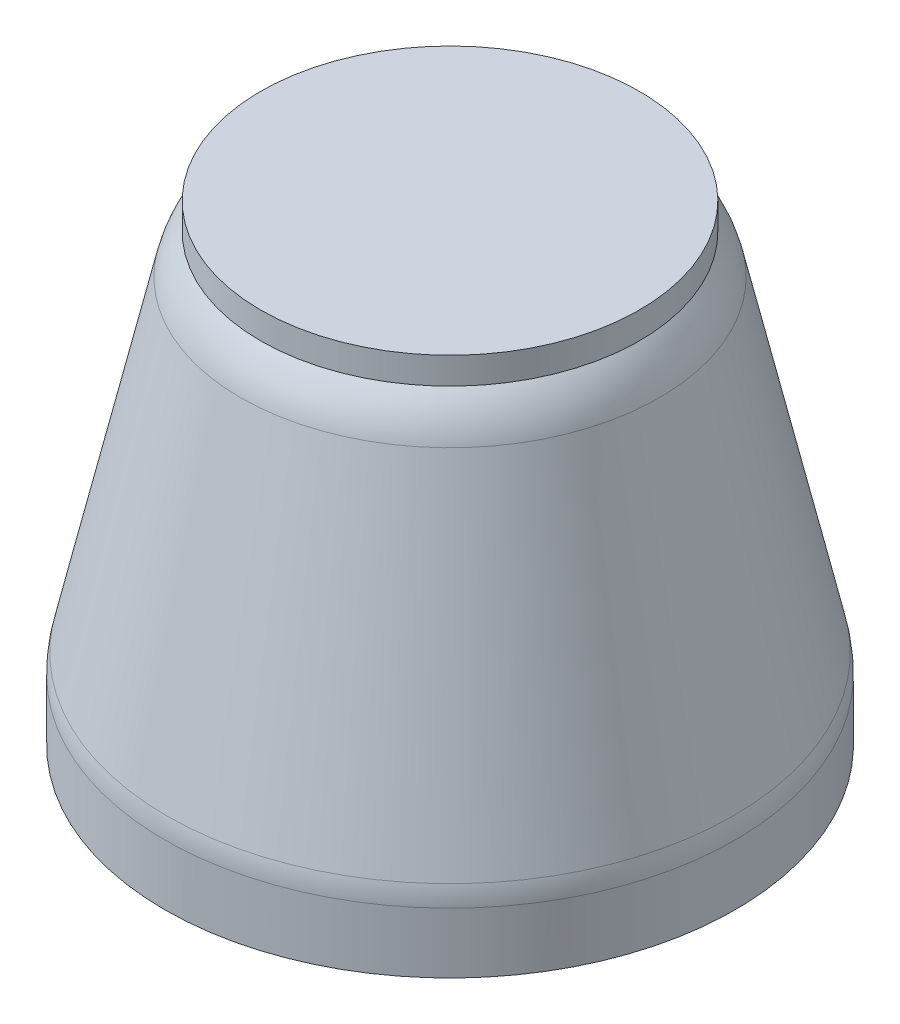
SolidWorks part; units mm, degrees
material "1060 Alloy"
ref_plane "Front Plane" through (0, 0, 0) normal (0, 0, 1) x (1, 0, 0)
ref_plane "Top Plane" through (0, 0, 0) normal (0, 1, 0) x (1, 0, 0)
ref_plane "Right Plane" through (0, 0, 0) normal (1, 0, 0) x (0, 0, -1)
sketch "Sketch1" plane through (0, 0, 0) normal (0, 1, 0) x (1, 0, 0)
  circle A1 centre (0, 0) radius 64
  circle A2 centre (0, 0) radius 64
  dimension "D2" = 128
  dimension "D3" = 128
extrude "Boss-Extrude1" add sketch "Sketch1" along normal blind 15.8 contours A1
ref_plane "Plane1" through (0, 99.8, 0) normal (0, 1, 0) x (1, 0, 0)
sketch "Sketch2" plane through (0, 99.8, 0) normal (0, 1, 0) x (1, 0, 0)
  circle A0 centre (0, 0) radius 45
  dimension "D1" = 90
loft "Loft1" add profiles "Sketch2" section edge at (0, 15.8, 64) section "Sketch2" connector at (-8.0213, 15.8, 63.4953) connector at (-12.7878, 99.8, 43.1448)
sketch "Sketch3" plane through (0, 99.8, 0) normal (0, 1, 0) x (1, 0, 0)
  circle A0 centre (0, 0) radius 42.5
  dimension "D1" = 85
extrude "Boss-Extrude2" add sketch "Sketch3" along normal blind 6
fillet "Fillet1" radius 20 2 edges at (0, 15.8, 64) (0, 99.8, 45)
sketch "Sketch4" plane through (0, 0, 0) normal (0, -1, 0) x (1, 0, 0)
  circle A0 centre (0, 0) radius 50
  dimension "D1" = 100
extrude "Cut-Extrude1" cut sketch "Sketch4" against normal blind 6 draft 20 contours A0
